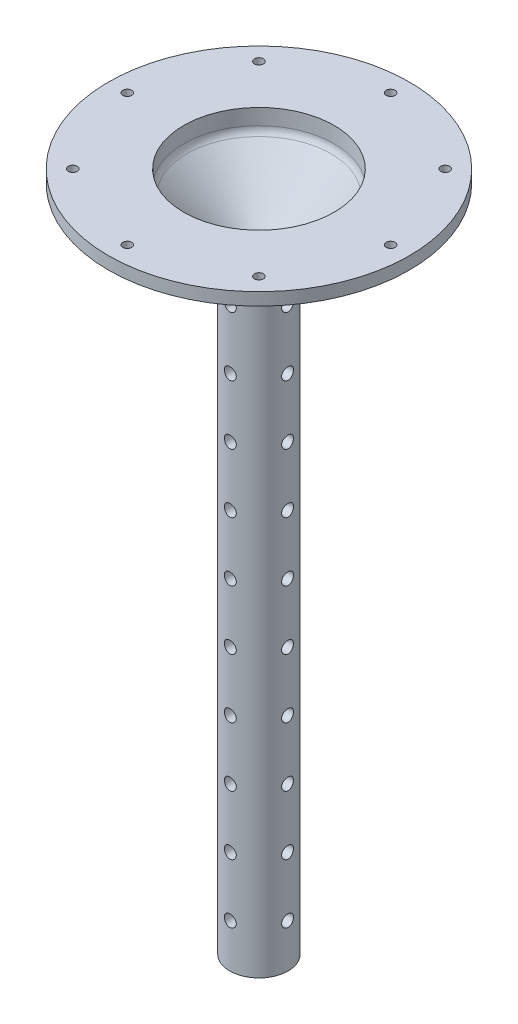
SolidWorks part; units mm, degrees
material "7075-T6 (SN)"
ref_plane "Front Plane" through (0, 0, 0) normal (0, 0, 1) x (1, 0, 0)
ref_plane "Top Plane" through (0, 0, 0) normal (0, 1, 0) x (1, 0, 0)
ref_plane "Right Plane" through (0, 0, 0) normal (1, 0, 0) x (0, 0, -1)
sketch "Sketch1" plane through (0, 0, 0) normal (0, 1, 0) x (1, 0, 0)
  circle A0 centre (0, 0) radius 38.1
  dimension "D1" = 76.2
extrude "Boss-Extrude1" add sketch "Sketch1" along normal blind 3.175
hole_wizard "Tap Drill for #4-40 Tap1" positions "Sketch3" profile "Sketch4" hole size "#4-40" standard "ANSI Inch" end condition through all
sketch "Sketch3" plane through (0, 0, 0) normal (0, -1, 0) x (-1, 0, 0)
  point P0 (0, -33.3375)
  dimension "D1" = 33.3375
sketch "Sketch4" plane through (0, 0, 33.3375) normal (1, 0, 0) x (0, 0, -1)
  line L0 (0, 0) -> (0, 3.175)
  line L1 (0, 3.175) -> (1.1303, 3.175)
  line L2 (1.1303, 3.175) -> (1.1303, 0)
  line L5 (1.1303, 0) -> (0, 0)
  line L11 (0, -6.35) -> (0, 107.95) construction
  dimension "Thru Hole Dia." = 2.2606
  dimension "Thru Hole Depth" = 3.175
pattern_circular "CirPattern1" count 8 over 360 about axis through (0, 0, 0) along (0, 1, 0) of "Tap Drill for #4-40 Tap1"
sketch "Sketch5" plane through (0, 0, 0) normal (0, -1, 0) x (1, 0, 0)
  circle A0 centre (0, 0) radius 25.4
  dimension "D1" = 50.8
extrude "Boss-Extrude2" add sketch "Sketch5" along normal blind 19.05
sketch "Sketch6" plane through (0, -19.05, 0) normal (0, -1, 0) x (1, 0, 0)
  circle A0 centre (0, 0) radius 4.7625
  dimension "D1" = 9.525
extrude "Cut-Extrude1" cut sketch "Sketch6" against normal through all both and the other way through all
sketch "Sketch7" plane through (0, 3.175, 0) normal (0, 1, 0) x (1, 0, 0)
  circle A0 centre (0, 0) radius 19.05
  dimension "D1" = 38.1
extrude "Cut-Extrude2" cut sketch "Sketch7" against normal blind 5.08
sketch "Sketch8" plane through (0, -1.905, 0) normal (0, 1, 0) x (1, 0, 0)
  circle A0 centre (0, 0) radius 19.05
  circle A1 centre (0, 0) radius 19.05 construction
  dimension "D1" = 0
ref_plane "Plane1" through (0, -15.875, 0) normal (0, -1, 0) x (-1, 0, 0)
sketch "Sketch9" plane through (0, -15.875, 0) normal (0, -1, 0) x (-1, 0, 0)
  circle A0 centre (0, 0) radius 4.7625
  circle A1 centre (0, 0) radius 4.7625 construction
  dimension "D1" = 0
loft "Cut-Loft1" cut profiles "Sketch8", "Sketch9" connector at (0, -1.905, 19.05) connector at (-1.301, -15.875, 4.5814)
chamfer "Chamfer1" distance 16.51 angle 45 1 edges at (0, -19.05, -25.4)
fillet "Fillet1" radius 2.54 1 edges at (0, 0, 25.4)
fillet "Fillet2" radius 2.54 1 edges at (0, -1.905, 19.05)
sketch "Sketch10" plane through (0, -19.05, 0) normal (0, -1, 0) x (1, 0, 0)
  circle A0 centre (0, 0) radius 4.7625
  circle A1 centre (0, 0) radius 7.39
  circle A2 centre (0, 0) radius 4.7625 construction
  circle A3 centre (0, 0) radius 8.89 construction
  dimension "D1" = 0
  dimension "D2" = 1.5
extrude "Boss-Extrude3" add sketch "Sketch10" along normal blind 150
sketch "Sketch11" plane through (0, 0, 0) normal (0, 0, 1) x (1, 0, 0)
  circle A0 centre (0, -23) radius 1.5
  dimension "D2" = 3
  dimension "D1" = 23
extrude "Cut-Extrude3" cut sketch "Sketch11" against normal through all both and the other way through all
pattern_circular "CirPattern2" count 4 over 360 about axis through (0, -169.05, 0) along (0, 1, 0) of "Cut-Extrude3" reverse direction yes
pattern_linear "LPattern1" count 10 spacing 15 along (0, -1, 0) of "Cut-Extrude3", "CirPattern2"
